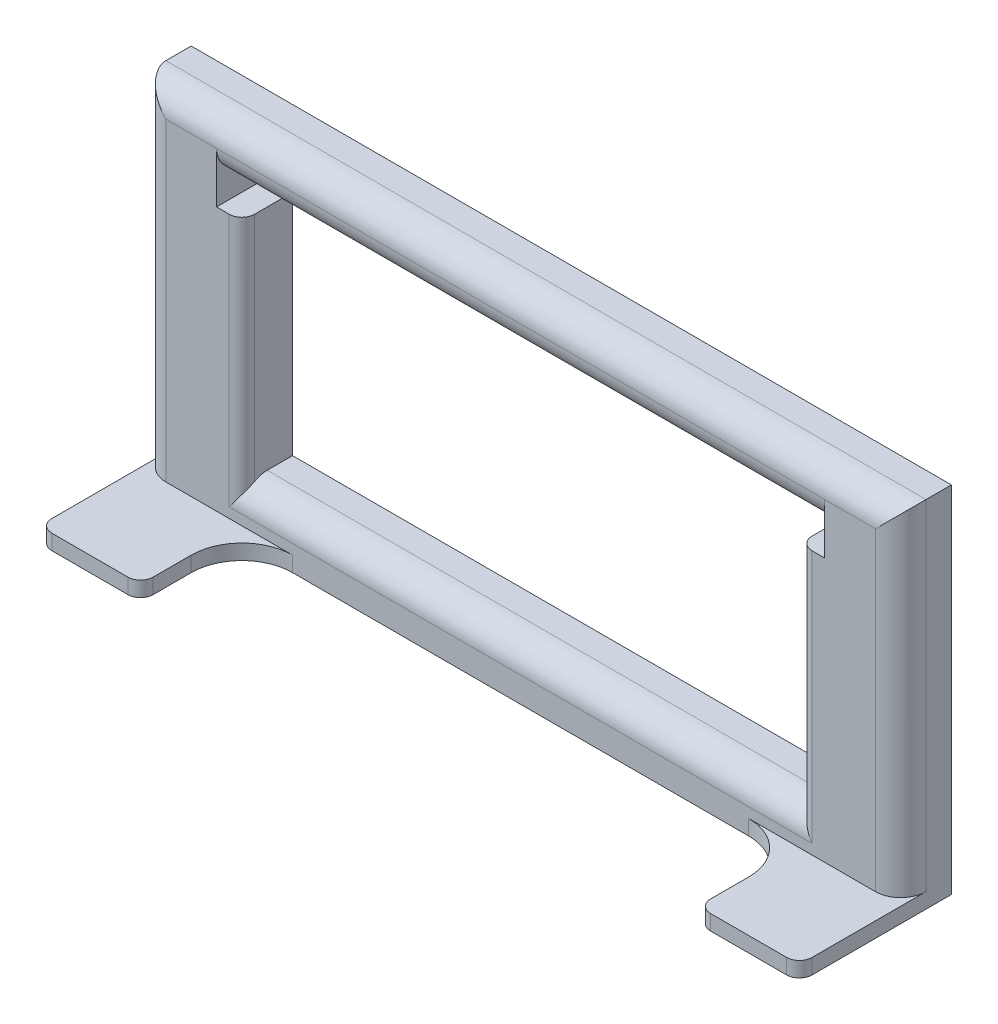
SolidWorks part; units mm, degrees
ref_plane "Front Plane" through (0, 0, 0) normal (0, 0, 1) x (1, 0, 0)
ref_plane "Top Plane" through (0, 0, 0) normal (0, 1, 0) x (1, 0, 0)
ref_plane "Right Plane" through (0, 0, 0) normal (1, 0, 0) x (0, 0, -1)
sketch "Sketch1" plane through (0, 0, 0) normal (0, 0, 1) x (1, 0, 0)
  line L1 (-55, 25) -> (55, 25)
  line L2 (-55, 25) -> (-55, -25)
  line L3 (-55, -25) -> (55, -25)
  line L4 (55, 25) -> (55, -25)
  line L5 (-55, 25) -> (55, -25) construction
  line L6 (-55, -25) -> (55, 25) construction
  line L7 (-75, 35) -> (75, 35)
  line L8 (-75, 35) -> (-75, -35)
  line L9 (-75, -35) -> (75, -35)
  line L10 (75, 35) -> (75, -35)
  line L11 (-75, 35) -> (75, -35) construction
  line L12 (-75, -35) -> (75, 35) construction
  line L13 (55, 25) -> (60, 25)
  line L14 (55, 25) -> (55, 20)
  line L15 (55, 20) -> (60, 20)
  line L16 (60, 25) -> (60, 20)
  line L17 (-55, 25) -> (-60, 25)
  line L18 (-55, 25) -> (-55, 20)
  line L19 (-55, 20) -> (-60, 20)
  line L20 (-60, 25) -> (-60, 20)
  point P0 (0, 0)
  point P6 (0, 0)
  dimension "D1" = 110
  dimension "D2" = 150
  dimension "D3" = 50
  dimension "D4" = 70
  dimension "D5" = 5
  dimension "D6" = 5
extrude "Boss-Extrude1" add sketch "Sketch1" along normal blind 10 contours L10 L7 L8 L9 L20 L17 L1 L13 L16 L15 L4 L3 L2 L19 region at (0, 33.3447, 0)
sketch "Sketch2" plane through (0, 0, 10) normal (0, 0, 1) x (1, 0, 0)
  line L0 (75, 35) -> (75, -35) construction
  line L1 (-75, -35) -> (75, -35)
  line L2 (-75, -35) -> (-75, -32)
  line L3 (-75, -32) -> (75, -32)
  line L4 (75, -35) -> (75, -32)
  dimension "D1" = 3
extrude "Boss-Extrude2" add sketch "Sketch2" along normal blind 20
sketch "Sketch3" plane through (0, -32, 0) normal (0, 1, 0) x (1, 0, 0)
  line L0 (60, 0) -> (55, 0) construction
  line L1 (55, 0) -> (55, -10) construction
  line L2 (55, -10) -> (60, -10) construction
  line L3 (60, -10) -> (60, 0) construction
  line L4 (75, -10) -> (-75, -10)
  line L5 (-75, -10) -> (-75, -30)
  line L6 (-75, -30) -> (75, -30)
  line L7 (75, -30) -> (75, -10)
  line L8 (75, -10) -> (-75, -10)
  line L9 (-75, -10) -> (-75, -30)
  line L10 (-75, -30) -> (75, -30)
  line L11 (75, -30) -> (75, -10)
  line L12 (-55, 0) -> (-60, 0) construction
  line L13 (-60, 0) -> (-60, -10) construction
  line L14 (-60, -10) -> (-55, -10) construction
  line L15 (-55, -10) -> (-55, 0) construction
  line L16 (60, 0) -> (55, 0)
  line L17 (55, 0) -> (55, -10)
  line L18 (55, -10) -> (60, -10)
  line L19 (60, -10) -> (60, 0)
  line L20 (-55, 0) -> (-60, 0)
  line L21 (-60, 0) -> (-60, -10)
  line L22 (-60, -10) -> (-55, -10)
  line L23 (-55, -10) -> (-55, 0)
  line L25 (-55, -10) -> (55, -10)
  line L26 (-55, -10) -> (-55, -30)
  line L27 (-55, -30) -> (55, -30)
  line L28 (55, -10) -> (55, -30)
  dimension "D1" = 0
extrude "Cut-Extrude1" cut sketch "Sketch3" against normal through all contours L28 L8 L26 L10 region at (0, -32, 20)
fillet "Fillet1" radius 5 5 edges at (-75, 1.5, 10) (75, 1.5, 10) (0, 35, 10) (0, 25, 10) (0, -25, 10)
fillet "Fillet2" radius 10 2 edges at (55, -33.5, 10) (-55, -33.5, 10)
fillet "Fillet3" radius 2.5 6 edges at (-55, -5, 10) (55, -5, 10) (75, -33.5, 30) (55, -33.5, 30) (-75, -33.5, 30) (-55, -33.5, 30)
